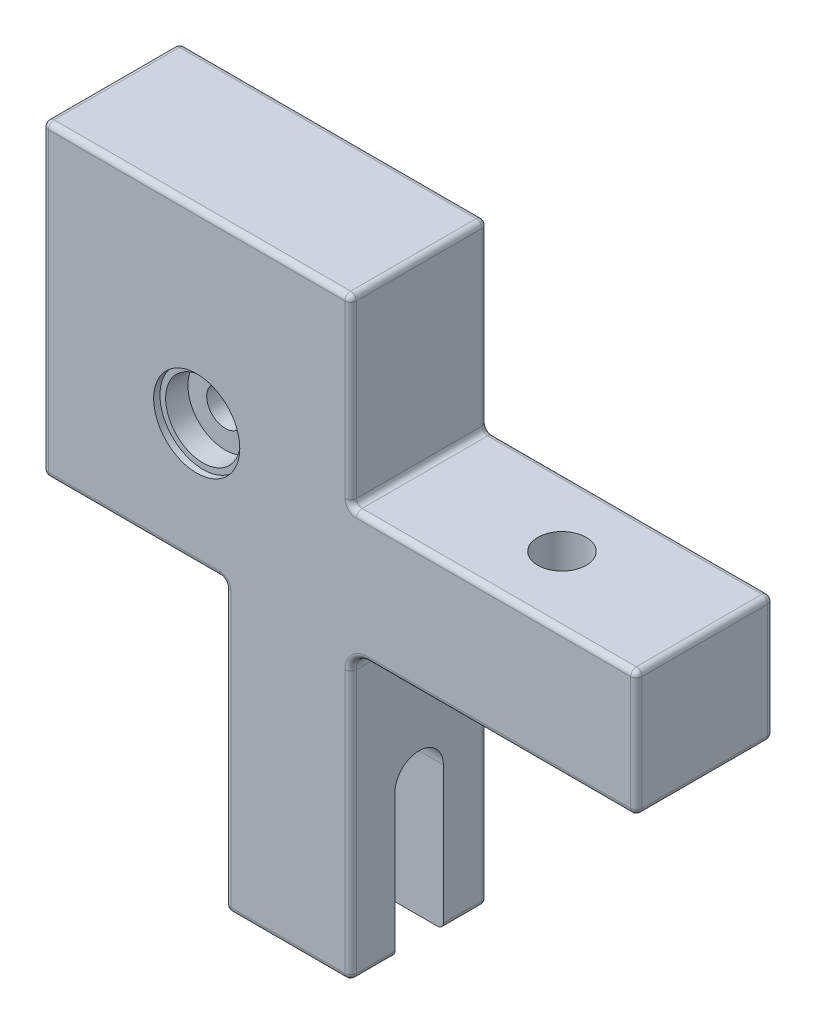
SolidWorks part; units mm, degrees
ref_plane "Plan de face" through (0, 0, 0) normal (0, 0, 1) x (1, 0, 0)
ref_plane "Plan de dessus" through (0, 0, 0) normal (0, 1, 0) x (1, 0, 0)
ref_plane "Plan de droite" through (0, 0, 0) normal (1, 0, 0) x (0, 0, -1)
sketch "Esquisse1" plane through (0, 0, 0) normal (0, 0, 1) x (1, 0, 0)
  line L0 (-25.05, 0) -> (25.05, 0)
  line L1 (25.05, 0) -> (25.05, 22)
  line L2 (25.05, 22) -> (-25.05, 22)
  line L5 (-25.05, 22) -> (-25.05, 54)
  line L6 (-25.05, 54) -> (-79.05, 54)
  line L7 (-79.05, 54) -> (-79.05, 0)
  line L9 (-25.05, 0) -> (-25.05, -50.1)
  line L10 (-25.05, -50.1) -> (-47.05, -50.1)
  line L13 (-79.05, 0) -> (-47.05, 0)
  line L14 (-47.05, 0) -> (-47.05, -50.1)
  point P4 (0, 0)
  dimension "D1" = 50.1
  dimension "D2" = 22
  dimension "D3" = 50.1
  dimension "D4" = 50.1
  dimension "D5" = 32
  dimension "D6" = 54
  dimension "D7" = 54
  dimension "D8" = 50.1
  dimension "D11" = 32
extrude "Boss.-Extru.1" add sketch "Esquisse1" against normal blind 24 contours L13 L14 L10 L9 L0 L1 L2 L5 L6 L7 region at (-37.4018, 12.3518, 0)
fillet "Congé1" radius 3 1 edges at (-25.05, 0, -12)
sketch "Esquisse2" plane through (0, 22, 0) normal (0, 1, 0) x (1, 0, 0)
  line L2 (0, 0) -> (0, 24) construction
  line L3 (25.05, 24) -> (-25.05, 24) construction
  circle A0 centre (0, 12) radius 4.25
  dimension "D1" = 8.5
extrude "Enlèv. mat.-Extru.1" cut sketch "Esquisse2" against normal through all
sketch "Esquisse3" plane through (-47.05, 0, 0) normal (-1, 0, 0) x (0, 0, 1)
  line L0 (0, 0) -> (0, -50.1) construction
  line L1 (0, -50.1) -> (0, -25.05) construction
  line L2 (0, -25.05) -> (-24, -25.05) construction
  line L3 (-24, 0) -> (-24, -50.1) construction
  circle A0 centre (-12, -25.05) radius 4.25
  dimension "D1" = 8.5
extrude "Enlèv. mat.-Extru.2" cut sketch "Esquisse3" against normal through all
sketch "Esquisse4" plane through (0, 0, 0) normal (0, 0, 1) x (1, 0, 0)
  line L0 (-67.05, 47.6) -> (-67.05, 21.4)
  line L1 (-67.05, 47.6) -> (-37.05, 47.6)
  line L2 (-37.05, 47.6) -> (-37.05, 21.4)
  line L3 (-67.05, 21.4) -> (-37.05, 21.4) construction
  line L12 (-79.05, 54) -> (-79.05, 0) construction
  line L13 (-25.05, 54) -> (-79.05, 54) construction
  arc A0 (-67.05, 21.4) -> (-37.05, 21.4) centre (-52.05, 21.4) ccw
  circle A1 centre (-52.05, 21.4) radius 3.25
  dimension "D5" = 6.5
  dimension "D1" = 26.2
  dimension "D2" = 30
  dimension "D3" = 27
  dimension "D4" = 6.4
extrude "Enlèv. mat.-Extru.3" cut sketch "Esquisse4" against normal blind 1.5
extrude "Enlèv. mat.-Extru.4" cut sketch "Esquisse4<2>" against normal through all contours A1 L3 | L3 A1 region at (-52.05, 22.7793, 0) region at (-52.05, 20.0207, 0)
sketch "Esquisse4<2>" plane through (0, 0, 0) normal (0, 0, 1) x (1, 0, 0) same geometry as "Esquisse4"
sketch "Esquisse5" plane through (0, 0, -24) normal (0, 0, -1) x (-1, 0, 0)
  circle A0 centre (52.05, 21.4) radius 7.55
  dimension "D1" = 15.1
extrude "Enlèv. mat.-Extru.5" [suppressed] cut sketch "Esquisse5" against normal blind 1.1
sketch "Esquisse6" plane through (0, 0, -24) normal (0, 0, -1) x (-1, 0, 0)
  circle A0 centre (52.05, 21.4) radius 6.55
  dimension "D1" = 13.1
extrude "Enlèv. mat.-Extru.6" [suppressed] cut sketch "Esquisse6" against normal blind 5
fillet "Congé2" radius 1 31 edges at (-63.05, 0, -24) (-63.05, 0, 0) (0, 22, -24) (0, 22, 0) (-25.05, -26.55, 0) (-24.1713, -0.8787, 0) (-25.05, -26.55, -24) (-24.1713, -0.8787, -24) (-25.05, -50.1, -12) (-36.05, -50.1, -24) (-36.05, -50.1, 0) (-47.05, -50.1, -12) (-47.05, -25.05, -24) (-47.05, 0, -12) (-47.05, -25.05, 0) (25.05, 22, -12) (25.05, 11, -24) (25.05, 0, -12) (25.05, 11, 0) (-25.05, 38, -24) (-25.05, 22, -12) (-25.05, 38, 0) (-79.05, 0, -12) (-79.05, 27, -24) (-79.05, 27, 0) (-79.05, 54, -12) (-52.05, 54, -24) (-25.05, 54, -12) (-52.05, 54, 0) (1.5, 0, 0) (1.5, 0, -24)
sketch "Esquisse7" plane through (0, 0, 0) normal (0, 0, 1) x (1, 0, 0)
  line L3 (-37.05, 47.6) -> (-67.05, 47.6)
  line L4 (-67.05, 47.6) -> (-67.05, 21.4)
  line L5 (-37.05, 21.4) -> (-37.05, 47.6)
  line L6 (-37.05, 47.6) -> (-67.05, 47.6)
  line L7 (-67.05, 47.6) -> (-67.05, 21.4)
  line L8 (-37.05, 21.4) -> (-37.05, 47.6)
  circle A0 centre (-52.05, 21.4) radius 3.25 construction
  arc A1 (-67.05, 21.4) -> (-37.05, 21.4) centre (-52.05, 21.4) ccw
  arc A2 (-67.05, 21.4) -> (-37.05, 21.4) centre (-52.05, 21.4) ccw
  circle A3 centre (-52.05, 21.4) radius 3.25
  line M18 (-67.05, 47.6) -> (-37.05, 47.6)
  line M19 (-37.05, 47.6) -> (-37.05, 21.4)
  arc M20 (-37.05, 21.4) -> (-67.05, 21.4) centre (-52.05, 21.4) cw
  line M21 (-67.05, 21.4) -> (-67.05, 47.6)
  dimension "D1" = 0
extrude "Boss.-Extru.2" add sketch "Esquisse7" against normal blind 3 contours A3 M18 M21 M20 M19 region at (-52.05, 28.6738, 0)
sketch "Esquisse8" plane through (0, 0, 0) normal (0, 0, 1) x (1, 0, 0)
  circle A0 centre (-52.05, 21.4) radius 7.55
  dimension "D1" = 15.1
extrude "Enlèv. mat.-Extru.7" cut sketch "Esquisse8" against normal blind 1.1
sketch "Esquisse9" plane through (0, 0, 0) normal (0, 0, 1) x (1, 0, 0)
  circle A0 centre (-52.05, 21.4) radius 6.55
  dimension "D1" = 13.1
extrude "Enlèv. mat.-Extru.8" cut sketch "Esquisse9" against normal blind 5
sketch "Esquisse10" [suppressed] plane through (0, 0, 0) normal (0, 0, 1) x (1, 0, 0)
  line L0 (-37.05, 21.4) -> (-37.05, 47.6) construction
  line L1 (-37.05, 47.6) -> (-67.05, 47.6) construction
  line L2 (-52.05, 21.4) -> (-52.05, 33.2231) construction
  circle A0 centre (-29.55, 37.6) radius 1.55
  circle A1 centre (-74.55, 37.6) radius 1.55
  dimension "D3" = 3.1
  dimension "D1" = 7.5
  dimension "D2" = 10
extrude "Enlèv. mat.-Extru.9" [suppressed] cut sketch "Esquisse10" against normal through all
sketch "Esquisse11" [suppressed] plane through (0, 0, 0) normal (0, 0, 1) x (1, 0, 0)
  line L0 (-26.05, 53) -> (-78.05, 53) construction
  line L1 (-27.95, 34.8287) -> (-26.35, 37.6)
  line L2 (-26.35, 37.6) -> (-27.95, 40.3713)
  line L3 (-27.95, 40.3713) -> (-31.15, 40.3713)
  line L4 (-31.15, 40.3713) -> (-32.75, 37.6)
  line L5 (-32.75, 37.6) -> (-31.15, 34.8287)
  line L6 (-31.15, 34.8287) -> (-27.95, 34.8287)
  circle A0 centre (-29.55, 37.6) radius 3.2 construction
  dimension "D1" = 6.4
extrude "Enlèv. mat.-Extru.11" [suppressed] cut sketch "Esquisse11" against normal blind 3 from offset 6 offset against normal yes
sketch "Esquisse13" [suppressed] plane through (-25.05, 0, 0) normal (1, 0, 0) x (0, 0, -1)
  line L0 (2, 54) -> (0, 54) construction
  line L3 (0, 54) -> (0, 53) construction
  line L4 (0, 53) -> (0, 34.83) construction
  line L5 (0, 23) -> (0, 53) construction
  line L6 (0, 34.83) -> (6, 34.83) construction
  line L8 (6, 34.83) -> (9, 34.83)
  line L9 (6, 34.83) -> (6, 40.37)
  line L10 (6, 40.37) -> (9, 40.37)
  line L11 (9, 34.83) -> (9, 40.37)
  point P4 (1, 54)
  dimension "D1" = 18.17
  dimension "D2" = 6
  dimension "D3" = 3
  dimension "D4" = 5.54
extrude "Enlèv. mat.-Extru.12" [suppressed] cut sketch "Esquisse13" against normal blind 3 contours L8 L11 L10 L9 | L9 L8 L11 L10
ref_plane "Plan1" [suppressed] through (-52.05, 0, 0) normal (-1, 0, 0) x (0, 0, 1)
mirror "Symétrie1" [suppressed] about plane through (-52.05, 0, 0) normal (-1, 0, 0)
sketch "Esquisse14" plane through (-47.05, 0, 0) normal (-1, 0, 0) x (0, 0, 1)
  line L0 (-16.25, -25.05) -> (-16.25, -50.1)
  line L5 (-1, -50.1) -> (-23, -50.1) construction
  line L6 (-7.75, -25.05) -> (-7.75, -50.1)
  line L7 (-7.75, -50.1) -> (-16.25, -50.1)
  circle A0 centre (-12, -25.05) radius 4.25 construction
  arc A1 (-7.75, -25.05) -> (-16.25, -25.05) centre (-12, -25.05) ccw
  dimension "D1" = 8.5
extrude "Enlèv. mat.-Extru.13" cut sketch "Esquisse14" against normal through all
